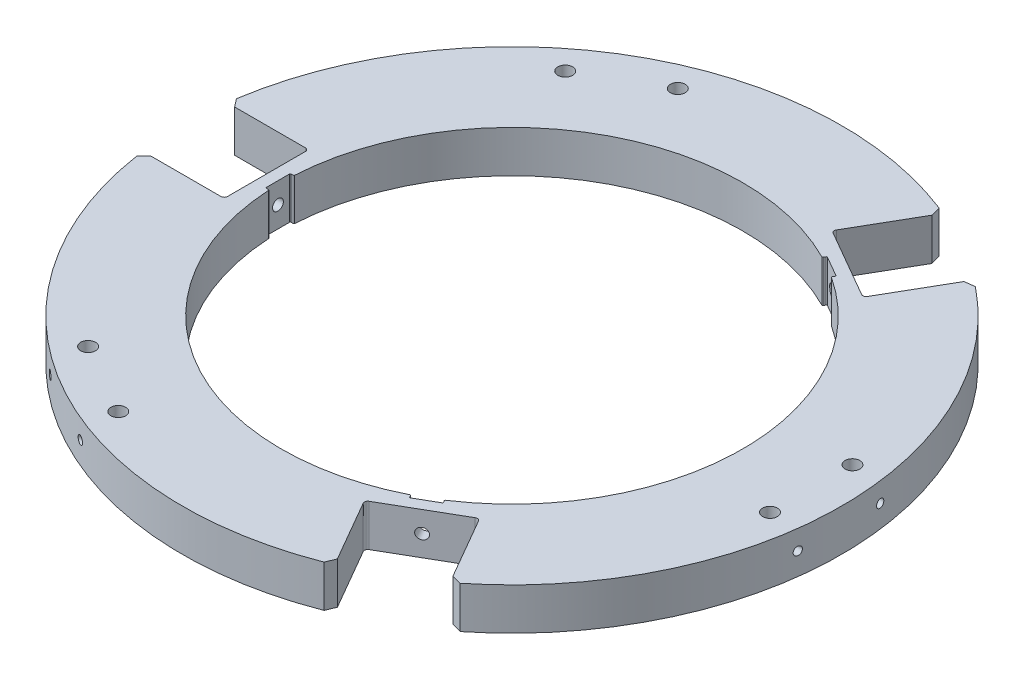
SolidWorks part; units mm, degrees
material "ABS"
ref_plane "Front Plane" through (0, 0, 0) normal (0, 0, 1) x (1, 0, 0)
ref_plane "Top Plane" through (0, 0, 0) normal (0, 1, 0) x (1, 0, 0)
ref_plane "Right Plane" through (0, 0, 0) normal (1, 0, 0) x (0, 0, -1)
sketch "Sketch1" plane through (0, 0, 0) normal (0, 1, 0) x (1, 0, 0)
  line L0 (73.8351, 102.2862) -> (51.6649, 115.0862)
  line L1 (-125.5, 12.8) -> (-74.5, 12.8)
  line L2 (-125.5, 12.8) -> (-125.5, -12.8)
  line L3 (-125.5, -12.8) -> (-74.5, -12.8)
  line L4 (-74.5, 12.8) -> (-74.5, -12.8)
  line L5 (-125.5, 12.8) -> (-74.5, -12.8) construction
  line L6 (-125.5, -12.8) -> (-74.5, 12.8) construction
  line L7 (73.8351, 102.2862) -> (48.3351, 58.1189)
  line L8 (48.3351, 58.1189) -> (26.1649, 70.9189)
  line L9 (51.6649, 115.0862) -> (26.1649, 70.9189)
  line L10 (51.6649, -115.0862) -> (73.8351, -102.2862)
  line L11 (51.6649, -115.0862) -> (26.1649, -70.9189)
  line L12 (26.1649, -70.9189) -> (48.3351, -58.1189)
  line L13 (73.8351, -102.2862) -> (48.3351, -58.1189)
  circle A0 centre (0, 0) radius 100
  circle A1 centre (0, 0) radius 70
  point P3 (-100, 0)
  point P18 (0, 0)
  dimension "D1" = 200
  dimension "D3" = 140
  dimension "D2" = 3
extrude "Boss-Extrude2" add sketch "Sketch1" along normal blind 12.7 contours L13 A0 L7 L8 L9 L1 L4 L3 L11 L12 region at (87.1009, 0, -43.0914)
fillet "Fillet1" radius 1 6 edges at (48.3351, 6.35, 58.1189) (26.1649, 6.35, 70.9189) (-74.5, 6.35, -12.8) (-74.5, 6.35, 12.8) (48.3351, 6.35, -58.1189) (26.1649, 6.35, -70.9189)
chamfer "Chamfer1" distance 2.5 angle 45 6 edges at (60.6738, 6.35, 79.4902) (38.5036, 6.35, 92.2902) (38.5036, 6.35, -92.2902) (60.6738, 6.35, -79.4902) (-99.1774, 6.35, -12.8) (-99.1774, 6.35, 12.8) first distance on face at (54.7545, 6.35, 69.2375) first distance on face at (-40.1685, 6.35, 69.5738) first distance on face at (32.5842, 6.35, -82.0375) first distance on face at (80.3369, 6.35, 0) first distance on face at (-40.1685, 6.35, -69.5738) first distance on face at (-87.3387, 6.35, 12.8)
hole_wizard "Ø3.0mm Dowel Hole2" positions "Sketch5" profile "Sketch6" hole size "Ø3.0" standard "ANSI Metric" end condition up to next
sketch "Sketch5" plane through (37.25, 0, 64.5189) normal (0.5, 0, 0.866) x (0.866, 0, -0.5)
  line L0 (-11.8, 12.7) -> (11.8, 12.7) construction
  line L1 (-11.8, 0) -> (11.8, 0) construction
  point P0 (0, 6.35)
  dimension "D1" = 6.35
  dimension "D2" = 6.35
sketch "Sketch6" plane through (37.25, 6.35, 64.5189) normal (0, 1, 0) x (0.866, 0, -0.5)
  line L0 (0, 0) -> (0, 4.5)
  line L1 (0, 4.5) -> (1.65, 4.5)
  line L2 (1.65, 4.5) -> (1.65, 0)
  line L5 (1.65, 0) -> (0, 0)
  line L11 (0, -6.35) -> (0, 107.95) construction
  dimension "Thru Hole Dia." = 3.3
  dimension "Thru Hole Depth" = 4.5
pattern_circular "CirPattern3" count 3 over 360 about axis through (0, 12.7, 0) along (0, -1, 0) of "Ø3.0mm Dowel Hole2"
sketch "Sketch8" plane through (0, 12.7, 0) normal (0, 1, 0) x (1, 0, 0)
  line L5 (0, 0) -> (-74.5, 0) construction
  line L6 (-74.5, 11.8) -> (-74.5, -11.8) construction
  line L8 (-71, 3.75) -> (-69, 3.75)
  line L9 (-71, 3.75) -> (-71, -3.75)
  line L10 (-71, -3.75) -> (-69, -3.75)
  line L11 (-69, 3.75) -> (-69, -3.75)
  line L12 (-71, 3.75) -> (-69, -3.75) construction
  line L13 (-71, -3.75) -> (-69, 3.75) construction
  arc A1 (-69.9806, 1.65) -> (-69.9806, -1.65) centre (0, 0) ccw construction
  point P4 (-70, 0)
  point P6 (-70, 0)
  dimension "D1" = 7.5
  dimension "D2" = 2
extrude "Cut-Extrude1" cut sketch "Sketch8" against normal through all
fillet "Fillet2" radius 0.25 4 edges at (-69.8995, 6.35, -3.75) (-69.8995, 6.35, 3.75) (-71, 6.35, 3.75) (-71, 6.35, -3.75)
pattern_circular "CirPattern4" count 3 over 360 about axis through (0, 12.7, 0) along (0, -1, 0) of "Fillet2", "Cut-Extrude1" reverse direction yes
sketch "Sketch9" plane through (0, 12.7, 0) normal (0, 1, 0) x (1, 0, 0)
  line L0 (0, 0) -> (-112.4513, 0) construction
  line L1 (0, 0) -> (37.25, 64.5189) construction
  line L2 (47.4691, 58.6189) -> (27.0309, 70.4189) construction
  line L3 (0, 0) -> (-54.9973, 95.2582) construction
  line L4 (0, 0) -> (135.0489, 0) construction
  line L5 (0, 0) -> (-63.6766, -110.2911) construction
  circle A0 centre (0, 0) radius 91.64 construction
  dimension "D4" = 183.28
  dimension "D1" = 60
  dimension "D2" = 60
  dimension "D3" = 60
hole_wizard "Ø4.0mm Dowel Hole1" positions "Sketch11" profile "Sketch12" hole size "Ø4.0" standard "ANSI Metric"
sketch "Sketch11" plane through (0, 12.7, 0) normal (0, 1, 0) x (1, 0, 0)
  line L0 (0, 0) -> (-54.9973, 95.2582) construction
  circle A0 centre (0, 0) radius 91.64 construction
  point P0 (-56.2171, 72.3708)
  point P4 (-34.5664, 84.8708)
  dimension "D1" = 12.5
  dimension "D2" = 12.5
sketch "Sketch12" plane through (-56.2171, 12.7, -72.3708) normal (1, 0, 0) x (0, 0, 1)
  line L0 (0, 0) -> (0, 46.3519)
  line L1 (0, 46.3519) -> (2.25, 45)
  line L2 (2.25, 45) -> (2.25, 0)
  line L5 (2.25, 0) -> (0, 0)
  line L10 (0, 46.3519) -> (-2.25, 45) construction
  line L11 (0, -6.35) -> (0, 107.95) construction
  dimension "Hole Dia." = 4.5
  dimension "Hole Depth" = 45
  dimension "Drill Angle" = 118
pattern_circular "CirPattern5" count 3 over 360 about axis through (0, 12.7, 0) along (0, -1, 0) of "Ø4.0mm Dowel Hole1" reverse direction yes
ref_plane "Plane1" through (89, 0, 0) normal (1, 0, 0) x (0, 0, -1)
sketch "Sketch13" plane through (89, 0, 0) normal (1, 0, 0) x (0, 0, -1)
  line L0 (0, 13.1263) -> (0, 0)
  point P3 (0, 0)
sketch "Sketch14" plane through (89, 0, 0) normal (1, 0, 0) x (0, 0, -1)
  line L0 (0, 13.1263) -> (12.5, 13.1263)
  line L1 (0, 13.1263) -> (-12.5, 13.1263)
  line L3 (12.5, 13.1263) -> (12.5, 6.7763)
  line L4 (-12.5, 13.1263) -> (-12.5, 6.7763)
  dimension "D1" = 12.5
  dimension "D2" = 12.5
  dimension "D3" = 6.35
  dimension "D4" = 6.35
hole_wizard "M3x0.5 Tapped Hole2" positions "3DSketch1" profile "Sketch15" tap size "M3x0.5" standard "ANSI Metric"
sketch3d "3DSketch1"
  point P0 (89, 6.7763, 12.5)
  point P3 (89, 6.7763, -12.5)
sketch "Sketch15" plane through (89, 6.7763, 12.5) normal (0, 1, 0) x (0, 0, 1)
  line L0 (0, 0) -> (0, 18.2511)
  line L1 (0, 18.2511) -> (1.25, 17.5)
  line L2 (1.25, 17.5) -> (1.25, 0)
  line L5 (1.25, 0) -> (0, 0)
  line L10 (0, 18.2511) -> (-1.25, 17.5) construction
  line L11 (0, -6.35) -> (0, 107.95) construction
  dimension "Tap Drill Dia." = 2.5
  dimension "Tap Drill Depth" = 17.5
  dimension "Drill Angle" = 118
cosmetic thread "Hole Thread7" parameters "D1"=6, "D2"=3
cosmetic thread "Hole Thread8" parameters "D1"=6, "D2"=3
pattern_circular "CirPattern6" count 3 over 360 about axis through (0, 12.7, 0) along (0, -1, 0) of "M3x0.5 Tapped Hole2" reverse direction yes
cosmetic thread "Hole Thread9" parameters "D1"=6, "D2"=3
cosmetic thread "Hole Thread10" parameters "D1"=6, "D2"=3
cosmetic thread "Hole Thread11" parameters "D1"=6, "D2"=3
cosmetic thread "Hole Thread12" parameters "D1"=6, "D2"=3
